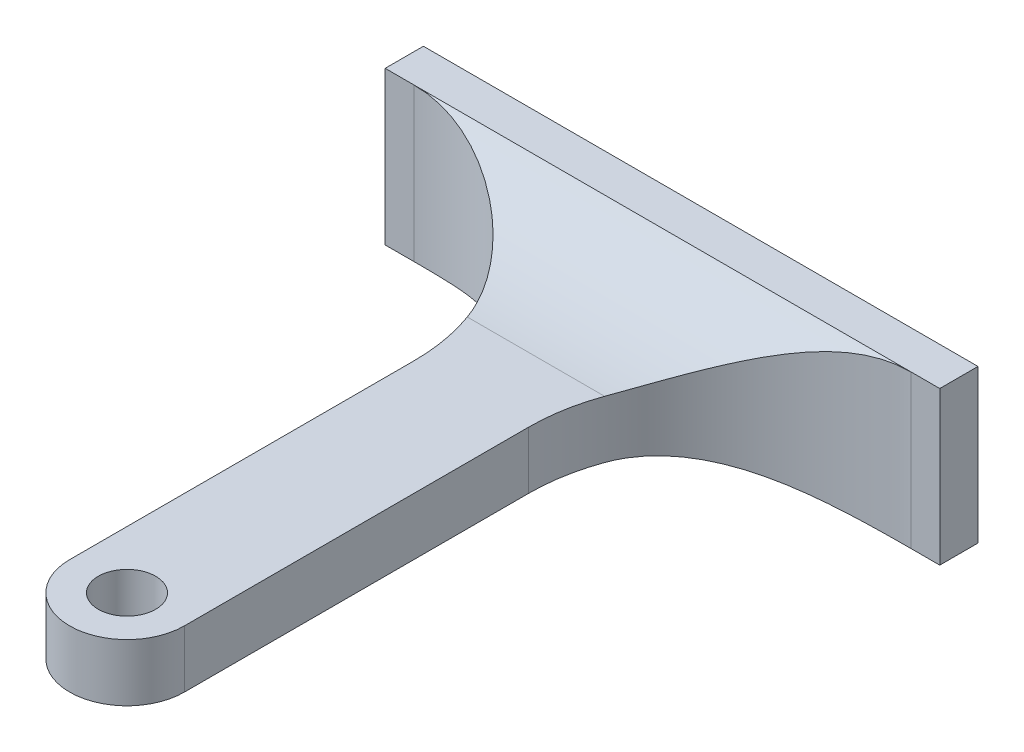
SolidWorks part; units mm, degrees
ref_plane "Top Plane" through (0, 0, 0) normal (0, 0, 1) x (1, 0, 0)
ref_plane "Right Plane" through (0, 0, 0) normal (0, 1, 0) x (1, 0, 0)
ref_plane "Front Plane" through (0, 0, 0) normal (1, 0, 0) x (0, 0, -1)
sketch "Sketch1" plane through (0, 0, 0) normal (0, 0, 1) x (1, 0, 0)
  line L0 (-14.5, 4) -> (-14.5, -4)
  line L1 (-15, 4.5) -> (15, 4.5) construction
  line L2 (-15, 4.5) -> (-15, -4.5) construction
  line L3 (-15, -4.5) -> (15, -4.5) construction
  line L4 (15, 4.5) -> (15, -4.5) construction
  line L5 (-15, 4.5) -> (15, -4.5) construction
  line L6 (-15, -4.5) -> (15, 4.5) construction
  line L7 (-14.5, -4) -> (14.5, -4)
  line L8 (14.5, 4) -> (14.5, -4)
  line L9 (-14.5, 4) -> (14.5, 4)
  point P4 (0, 0)
  point P5 (0, 0)
  dimension "D1" = 9
  dimension "D2" = 30
  dimension "D3" = 0.5
extrude "Boss-Extrude1" add sketch "Sketch1" along normal blind 2
sketch "Sketch2" plane through (0, 0, 0) normal (0, 1, 0) x (1, 0, 0)
  line L0 (-3, -2) -> (3, -2)
  line L1 (3, -2) -> (3, -30)
  line L2 (-3, -30) -> (-3, -2)
  line L3 (0, -2) -> (0, 0) construction
  line L4 (-14.5, -2) -> (14.5, -2) construction
  arc A0 (3, -30) -> (-3, -30) centre (0, -30) cw
  circle A1 centre (0, -30) radius 1.5
  dimension "D3" = 3
  dimension "D1" = 30
  dimension "D2" = 6
extrude "Boss-Extrude2" add sketch "Sketch2" along normal mid plane 3
fillet "Fillet1" radius 10 4 edges at (-3, 0, 2) (0, 1.5, 2) (3, 0, 2) (0, -1.5, 2)
